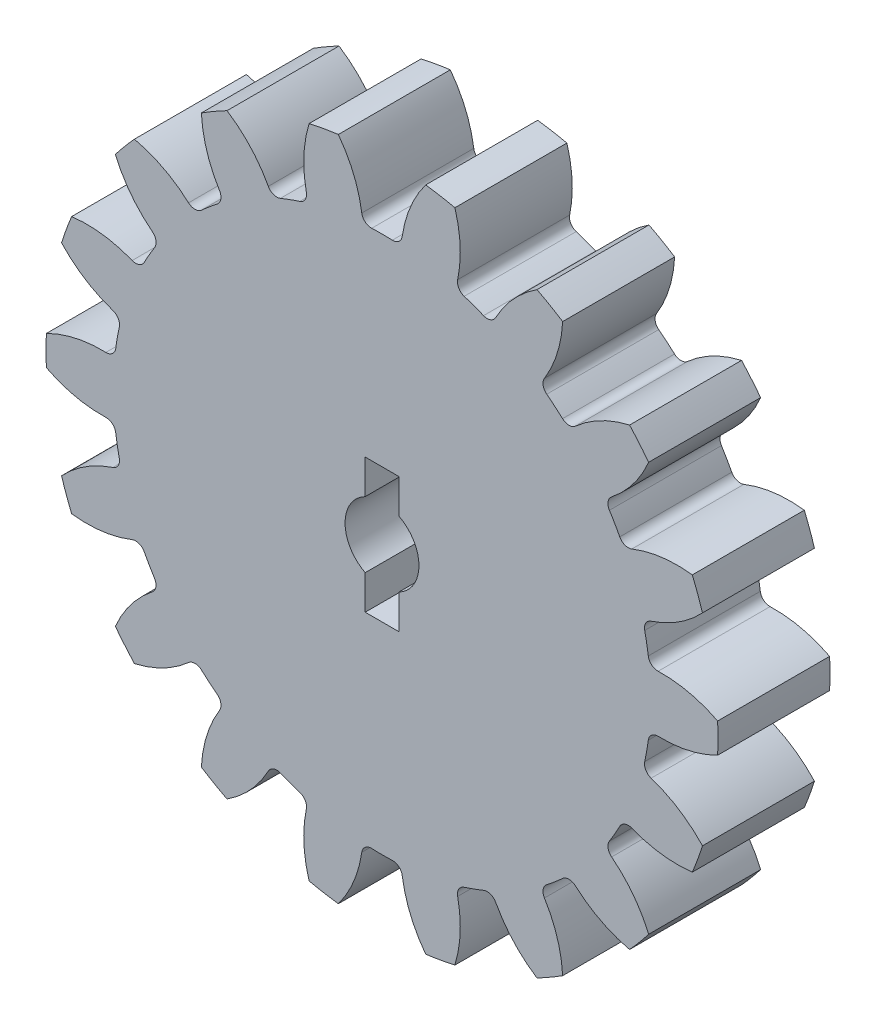
SolidWorks part; units mm, degrees
ref_plane "Front" through (0, 0, 0) normal (0, 0, 1) x (1, 0, 0)
ref_plane "Top" through (0, 0, 0) normal (0, 1, 0) x (1, 0, 0)
ref_plane "Right" through (0, 0, 0) normal (1, 0, 0) x (0, 0, -1)
sketch "Sketch1" plane through (0, 0, 0) normal (0, 0, 1) x (1, 0, 0)
  circle A0 centre (0, 0) radius 12
  circle A1 centre (0, 0) radius 15
  circle A2 centre (0, 0) radius 13.5
  dimension "D1" = 30
  dimension "D2" = 24
  dimension "D3" = 27
extrude "Boss-Extrude1" add sketch "Sketch1" along normal mid plane 5 contours A1
sketch "Sketch3" plane through (0, 0, 0) normal (0, 0, 1) x (1, 0, 0)
  line L0 (0, 0) -> (0, 15) construction
  line L1 (0, 0) -> (-0.8606, 11.9691) construction
  line L2 (-1.1766, 13.4486) -> (1.1766, 13.4486) construction
  line L3 (-1.7058, 14.9027) -> (0, 10.2159) construction
  line L4 (1.1766, 13.4486) -> (3.4941, 13.04) construction
  line L5 (2.6047, 14.7721) -> (0, 0) construction
  arc A0 (-0.8606, 11.9691) -> (0.8606, 11.9691) centre (0, 0) cw
  arc A4 (1.9502, 14.8727) -> (-1.9502, 14.8727) centre (0, 0) ccw
  circle A5 centre (0, 0) radius 15 construction
  arc A7 (-1.9502, 14.8727) -> (-0.8606, 11.9691) centre (-6.3201, 11.5766) cw
  arc A10 (1.9502, 14.8727) -> (0.8606, 11.9691) centre (6.3201, 11.5766) ccw
  circle A11 centre (0, 0) radius 12 construction
  circle A12 centre (0, 0) radius 13.5 construction
  dimension "D1" = 20
  dimension "D2" = 10
extrude "Cut-Extrude1" cut sketch "Sketch3" against normal through all both and the other way through all contours A10 A4 A7 A0 region at (0, 13.6934, 0)
fillet "Fillet2" radius 0.43 2 edges at (-0.8606, 11.9691, 0) (0.8606, 11.9691, 0)
pattern_circular "CirPattern1" count 18 over 360 about axis through (0, 0, 2.5) along (0, 0, -1) of "Cut-Extrude1", "Fillet2"
sketch "Sketch4" plane through (0, 0, 0) normal (0, 0, 1) x (1, 0, 0)
  line L0 (-0.75, 3) -> (0.75, 3)
  line L1 (-0.75, -3) -> (0.75, -3) construction
  line L3 (-0.75, 3) -> (0.75, 3) construction
  line L7 (0.75, 3) -> (0.75, 1.4697)
  line L8 (-0.75, 3) -> (-0.75, 1.4697)
  line L9 (-0.75, -1.4697) -> (-0.75, -3)
  line L10 (-0.75, -3) -> (0.75, -3)
  line L11 (0.75, -3) -> (0.75, -1.4697)
  arc A1 (-0.75, 1.4697) -> (-0.75, -1.4697) centre (0, 0) ccw
  arc A2 (0.75, 1.4697) -> (0.75, -1.4697) centre (0, 0) cw
  dimension "D1" = 1.65
  dimension "D4" = 1.65
  dimension "D2" = 6
  dimension "D3" = 1.5
  dimension "D5" = 1.5
  dimension "D6" = 1.5303
extrude "Through_Center_Hole" cut sketch "Sketch4" against normal through all both and the other way through all
sketch "Sketch5" plane through (0, 0, 2.5) normal (0, 0, 1) x (1, 0, 0)
  circle A0 centre (0, 0) radius 1.6476
  dimension "D1" = 3.2952
equation "\"od\"= 30'outside diameter"
equation "\"n\"= 18'number of teeth"
equation "\"m\"= \"od\" / ( \"n\" + 2 )'module"
equation "\"p\"= \"m\" * pi'pitch"
equation "\"d\"= \"m\" * \"n\"'primitive diameter"
equation "\"da\"= \"d\" + 2 * \"m\"'head diamater"
equation "\"df\"= \"d\" - 2 * \"m\"'foot diameter"
equation "\"D1@Sketch1\"=\"od\""
equation "\"D2@Sketch1\"=\"df\""
equation "\"D3@Sketch1\"=\"d\""
equation "\"D2@Sketch3\"=180/\"n\""
equation "\"D1@CirPattern1\"=\"n\""
